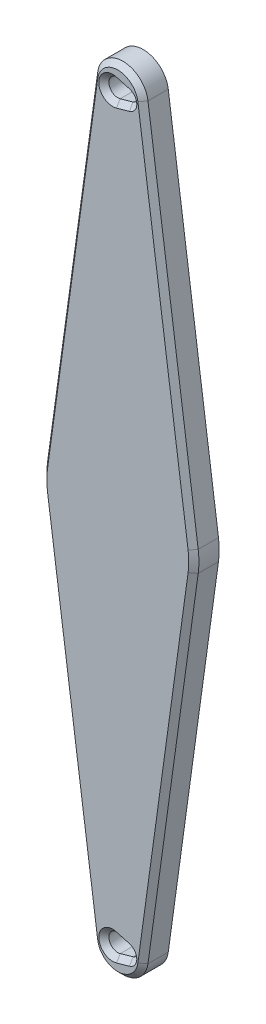
SolidWorks part; units mm, degrees
ref_plane "Front Plane" through (0, 0, 0) normal (0, 0, 1) x (1, 0, 0)
ref_plane "Top Plane" through (0, 0, 0) normal (0, 1, 0) x (1, 0, 0)
ref_plane "Right Plane" through (0, 0, 0) normal (1, 0, 0) x (0, 0, -1)
sketch "Sketch1" plane through (0, 0, 0) normal (0, 0, 1) x (1, 0, 0)
  line L1 (191, 68) -> (85, 68)
  line L2 (85, 68) -> (85, 141) construction
  line L3 (89.9529, 141.6849) -> (99.8586, 70.0548)
  line L8 (0, 136) -> (0, 0)
  line L9 (0, 0) -> (191, 0)
  line L10 (191, 0) -> (191, 136)
  line L11 (191, 136) -> (0, 136)
  line L12 (80.0471, 141.6849) -> (70.1414, 70.0548)
  line L13 (89.9529, -5.6849) -> (99.8586, 65.9452)
  line L14 (80.0471, -5.6849) -> (70.1414, 65.9452)
  circle A0 centre (85, 68) radius 15
  circle A1 centre (85, 141) radius 5
  circle A2 centre (85, -5) radius 5
  dimension "D2" = 30
  dimension "D4" = 10
  dimension "D3" = 5
extrude "Boss-Extrude1" add sketch "Sketch1" along normal blind 5 contours L2 A0 L3 L11 | A0 L2 L11 L12 | A1 | A1 L11 L3 | A1 L12 L11 | L1 L2 A0 | L2 L1 A0 | A0 L14 L9 L13 | L14 A2 L9 | L9 A2 L13 | A2 region at (82.8779, 65.8779, 0) region at (91.3662, 74.3662, 0) region at (90.3088, 104.3689, 0) region at (85, 31.6311, 0) region at (89.2502, -1.2971, 0) region at (89.2502, 137.2971, 0) region at (79.6912, 104.3689, 0) region at (80.7498, -1.2971, 0) region at (85, -5, 0) region at (89.8471, 141.3336, 0) region at (80.7498, 137.2971, 0)
chamfer "Chamfer1" distance 1 angle 45 8 edges at (75.0943, 30.1301, 5) (70, 68, 5) (75.0943, 105.8699, 5) (85, 146, 5) (94.9057, 105.8699, 5) (100, 68, 5) (94.9057, 30.1301, 5) (85, -10, 5)
sketch "Sketch6" plane through (0, 0, 5) normal (0, 0, 1) x (1, 0, 0)
  line L0 (85, 141) -> (84, 141) construction
  line L1 (85, 141) -> (86.75, 141) construction
  line L2 (84.4773, 139.3163) -> (87.0227, 140.0379)
  line L3 (84.4773, 142.6837) -> (87.0227, 141.9621)
  circle A0 centre (84, 141) radius 1.75
  circle A1 centre (86.75, 141) radius 1
  dimension "D1" = 1
  dimension "D2" = 3.5
  dimension "D4" = 2
  dimension "D3" = 1.75
extrude "Cut-Extrude2" cut sketch "Sketch6" against normal up to next contours A1 L3 A0 L2 | A1 | A0 | A1 A0 L2 region at (85.7876, 139.9859, 5) region at (84, 141, 5) region at (86.75, 141, 5) region at (85.7876, 142.0141, 5)
chamfer "Chamfer3" distance 1 angle 45 8 edges at (85.75, 139.6771, 0) (87.75, 141, 0) (82.25, 141, 0) (85.75, 142.3229, 0) (87.75, 141, 5) (85.75, 139.6771, 5) (82.25, 141, 5) (85.75, 142.3229, 5)
sketch "Sketch7" plane through (0, 0, 5) normal (0, 0, 1) x (1, 0, 0)
  line L1 (190.9692, 65.4461) -> (85, 68) construction
  line L2 (190.9692, 65.4461) -> (85, 68) construction
ref_axis "Axis2" through (85, 68, 5) along (0, 0, -1)
sketch "Sketch8" plane through (0, 0, 0) normal (0, 0, -1) x (-1, 0, 0)
  line L0 (-100, 68) -> (-70, 68) construction
  arc A0 (-99.8586, 70.0548) -> (-99.8586, 65.9452) centre (-85, 68) ccw construction
  arc A1 (-70.1414, 65.9452) -> (-70.1414, 70.0548) centre (-85, 68) ccw construction
ref_axis "Axis3" through (100, 68, 0) along (-1, 0, 0)
ref_plane "Plane3" through (0, 68, 0) normal (0, -1, 0) x (-1, 0, 0)
mirror "Mirror2" about plane through (0, 68, 0) normal (0, -1, 0) of "Cut-Extrude2", "Chamfer3"
